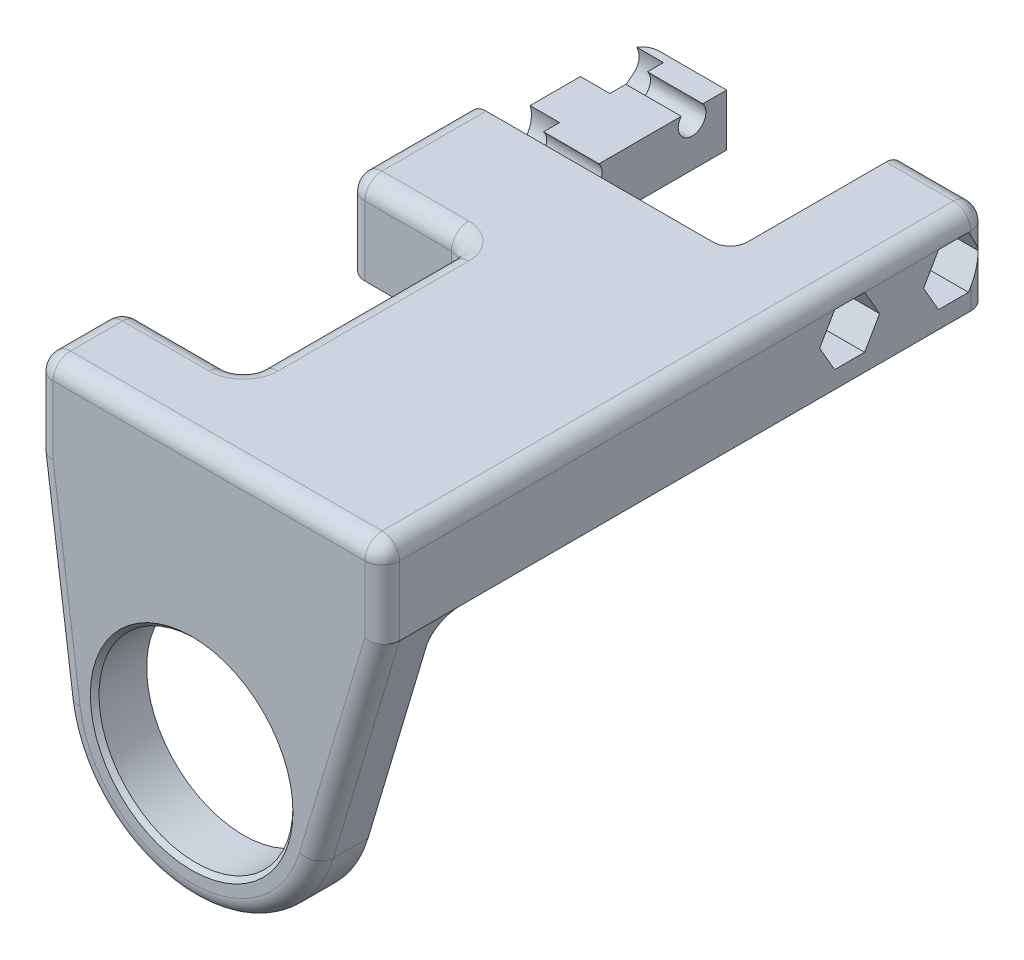
SolidWorks part; units mm, degrees
ref_plane "Top Plane" through (0, 0, 0) normal (0, 0, 1) x (1, 0, 0)
ref_plane "Right Plane" through (0, 0, 0) normal (0, 1, 0) x (1, 0, 0)
ref_plane "Front Plane" through (0, 0, 0) normal (1, 0, 0) x (0, 0, -1)
sketch "Sketch1" plane through (0, 0, 0) normal (0, 0, 1) x (1, 0, 0)
  line L0 (0, 0) -> (0, 31.25) construction
  line L1 (22, 31.25) -> (22, 21.25)
  line L2 (-18, 31.25) -> (22, 31.25)
  line L3 (-18, 31.25) -> (-18, 21.25)
  line L4 (22, 21.25) -> (14.3729, -4.2919)
  line L5 (-18, 21.25) -> (-14.8656, -2.0038)
  line L6 (-18, 21.25) -> (22, 21.25) construction
  arc A0 (-14.8656, -2.0038) -> (14.3729, -4.2919) centre (0, 0) ccw construction
  circle A1 centre (0, 0) radius 11 construction
  circle A2 centre (0, 0) radius 4 construction
  arc A3 (-14.8656, -2.0038) -> (14.3729, -4.2919) centre (0, 0) ccw
  dimension "D1" = 30
  dimension "D2" = 22
  dimension "D3" = 8
  dimension "D6" = 10
  dimension "D4" = 21.25
  dimension "D5" = 40
  dimension "D7" = 18
extrude "Boss-Extrude1" add sketch "Sketch1" along normal blind 6
sketch "Sketch2" plane through (0, 0, 6) normal (0, 0, 1) x (1, 0, 0)
  circle A2 centre (0, 0) radius 11.2
  circle A3 centre (0, 0) radius 11.2
  dimension "D1" = 0.2
extrude "Cut-Extrude1" cut sketch "Sketch2" against normal through all
sketch "Sketch3" plane through (0, 0, 0) normal (0, 0, -1) x (-1, 0, 0)
  line L0 (18, 31.25) -> (-22, 31.25) construction
  line L1 (-22, 31.25) -> (-12, 31.25) construction
  line L2 (-22, 31.25) -> (-22, 21.25) construction
  line L3 (-22, 21.25) -> (-12, 21.25) construction
  line L4 (-12, 31.25) -> (-12, 21.25) construction
  line L5 (8, 31.25) -> (18, 31.25) construction
  line L6 (8, 31.25) -> (8, 21.25) construction
  line L7 (8, 21.25) -> (18, 21.25) construction
  line L8 (18, 31.25) -> (18, 21.25) construction
  line L9 (-12, 26.25) -> (8, 26.25) construction
  line L11 (-2, 26.25) -> (-2, 31.25) construction
  line L13 (-22, 31.25) -> (18, 31.25)
  line L14 (-22, 31.25) -> (-22, 21.25)
  line L15 (-22, 21.25) -> (18, 21.25)
  line L16 (18, 31.25) -> (18, 21.25)
  point P12 (-2, 26.25)
  dimension "D1" = 20
extrude "Boss-Extrude2" add sketch "Sketch3" along normal blind 44
sketch "Sketch4" plane through (0, 0, -44) normal (0, 0, -1) x (-1, 0, 0)
  line L0 (-22, 21.25) -> (18, 21.25) construction
  line L1 (-22, 31.25) -> (-12.2, 31.25)
  line L2 (-22, 31.25) -> (-22, 21.25)
  line L3 (-22, 21.25) -> (-12.2, 21.25)
  line L4 (-12.2, 31.25) -> (-12.2, 21.25)
  line L5 (8.2, 27.25) -> (18, 27.25)
  line L6 (8.2, 27.25) -> (8.2, 21.25)
  line L7 (8.2, 21.25) -> (18, 21.25)
  line L8 (18, 27.25) -> (18, 21.25)
  line L9 (-12, 31.25) -> (-12, 21.25) construction
  line L10 (8, 31.25) -> (8, 21.25) construction
  dimension "D1" = 0.2
  dimension "D2" = 0.2
extrude "Boss-Extrude3" add sketch "Sketch4" along normal blind 20
fillet "Fillet1" radius 3 1 edges at (2, 21.25, 0)
sketch "Sketch5" plane through (12.2, 0, 0) normal (-1, 0, 0) x (0, 0, 1)
  line L0 (-64, 26.25) -> (-44, 26.25) construction
  line L1 (-64, 21.25) -> (-64, 31.25) construction
  line L2 (-44, 21.25) -> (-44, 31.25) construction
  line L3 (-54, 31.25) -> (-54, 26.25) construction
  line L4 (-64, 31.25) -> (-44, 31.25) construction
  circle A0 centre (-60, 26.25) radius 1.75
  circle A1 centre (-48, 26.25) radius 1.75
  dimension "D1" = 3.5
  dimension "D2" = 12
hole_wizard "CBORE for M3 Hex Socket Head Cap Screw1" positions "Sketch6" profile "Sketch7" counterbore size "M3" standard "ISO" end condition through all
sketch "Sketch6" plane through (-18, 0, 0) normal (-1, 0, 0) x (0, 0, 1)
  point P0 (-60, 26.25)
  point P3 (-48, 26.25)
sketch "Sketch7" plane through (-18, 26.25, -60) normal (0, 1, 0) x (0, 0, 1)
  line L0 (0, 0) -> (0, 40)
  line L1 (0, 40) -> (1.6, 40)
  line L3 (1.6, 40) -> (1.6, 3.4)
  line L4 (1.6, 3.4) -> (3.25, 3.4)
  line L5 (3.25, 3.4) -> (3.25, 0)
  line L7 (3.25, 0) -> (0, 0)
  line L11 (0, -6.35) -> (0, 107.95) construction
  dimension "Thru Hole Dia." = 3.2
  dimension "Thru Hole Depth" = 40
  dimension "C'Bore Dia." = 6.5
  dimension "C'Bore Depth" = 3.4
sketch "Sketch8" plane through (22, 0, 0) normal (1, 0, 0) x (0, 0, -1)
  line L1 (49.7321, 29.25) -> (46.2679, 29.25)
  line L2 (46.2679, 29.25) -> (44.5359, 26.25)
  line L3 (44.5359, 26.25) -> (46.2679, 23.25)
  line L4 (46.2679, 23.25) -> (49.7321, 23.25)
  line L5 (49.7321, 23.25) -> (51.4641, 26.25)
  line L6 (51.4641, 26.25) -> (49.7321, 29.25)
  line L7 (58.2679, 29.25) -> (56.5359, 26.25)
  line L8 (56.5359, 26.25) -> (58.2679, 23.25)
  line L9 (58.2679, 23.25) -> (61.7321, 23.25)
  line L10 (61.7321, 23.25) -> (63.4641, 26.25)
  line L11 (63.4641, 26.25) -> (61.7321, 29.25)
  line L12 (61.7321, 29.25) -> (58.2679, 29.25)
  circle A0 centre (48, 26.25) radius 3 construction
  circle A1 centre (60, 26.25) radius 3 construction
  dimension "D1" = 6
extrude "Cut-Extrude3" cut sketch "Sketch8" against normal offset from surface (5.8 mm away) 4 up to face at (12.2, 27.85, -60)
sketch "Sketch9" plane through (0, 31.25, 0) normal (0, 1, 0) x (1, 0, 0)
  line L0 (-18, -6) -> (-18, 44) construction
  line L1 (-18, 30) -> (-4, 30)
  line L2 (-18, 30) -> (-18, 4)
  line L3 (-18, 4) -> (-4, 4)
  line L4 (-4, 30) -> (-4, 4)
  line L5 (22, -6) -> (-18, -6) construction
  dimension "D1" = 36
  dimension "D2" = 10
  dimension "D3" = 14
extrude "Cut-Extrude4" cut sketch "Sketch9" against normal through all
fillet "Fillet2" radius 2 2 edges at (-4, 26.25, -4) (-4, 26.25, -30)
fillet "Fillet3" radius 2 2 edges at (12.2, 26.25, -44) (-8.2, 24.25, -44)
fillet "Fillet4" radius 2 9 edges at (-16.4328, 9.6231, 6) (-1.1703, -14.9543, 6) (18.1864, 8.479, 6) (-18, 26.25, 6) (22, 26.25, 6) (-18, 26.25, -4) (-18, 26.25, -30) (22, 26.25, -64) (-18, 24.25, -64)
fillet "Fillet5" radius 2 15 edges at (-18, 31.25, -38) (-17.4142, 31.25, -30.5858) (-11, 31.25, -30) (-4.5858, 31.25, -29.4142) (-4, 31.25, -17) (-4.5858, 31.25, -4.5858) (-11, 31.25, -4) (-17.4142, 31.25, -3.4142) (-18, 31.25, 1) (-17.4142, 31.25, 5.4142) (2, 31.25, 6) (21.4142, 31.25, 5.4142) (16.1, 31.25, -64) (21.4142, 31.25, -63.4142) (22, 31.25, -29)
chamfer "Chamfer1" distance 0.5 angle 45 1 edges at (11.2, 0, 6)
